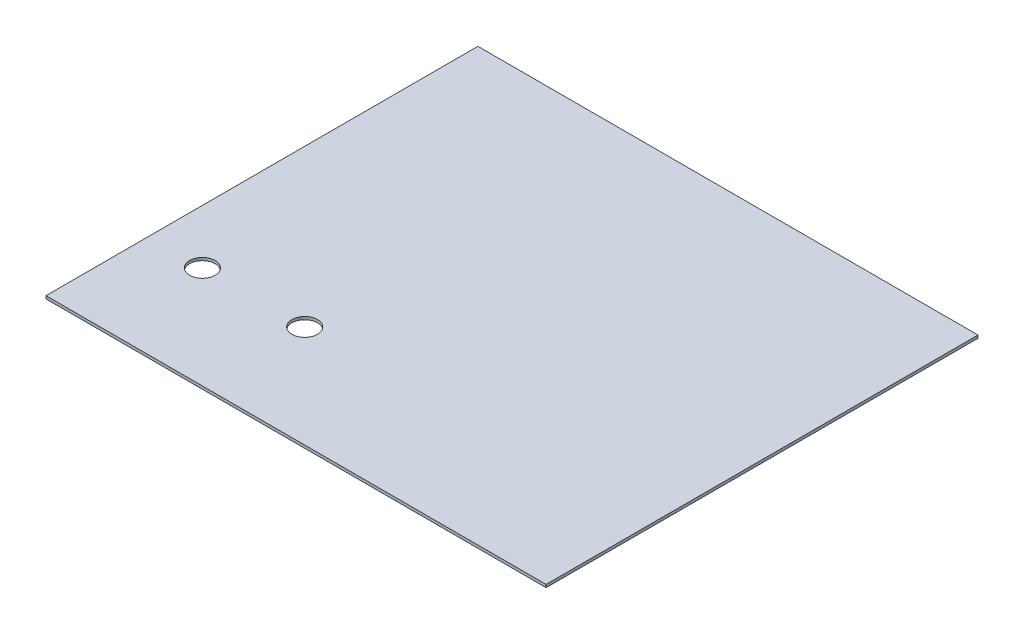
SolidWorks part; units mm, degrees
ref_plane "Front Plane" through (0, 0, 0) normal (0, 0, 1) x (1, 0, 0)
ref_plane "Top Plane" through (0, 0, 0) normal (0, 1, 0) x (1, 0, 0)
ref_plane "Right Plane" through (0, 0, 0) normal (1, 0, 0) x (0, 0, -1)
sketch "Sketch1" plane through (0, 0, 0) normal (0, 1, 0) x (1, 0, 0)
  line L1 (0, 0) -> (558.8, 0)
  line L2 (0, 0) -> (0, 482.6)
  line L3 (0, 482.6) -> (558.8, 482.6)
  line L4 (558.8, 0) -> (558.8, 482.6)
  dimension "D1" = 558.8
  dimension "D2" = 482.6
extrude "Boss-Extrude1" add sketch "Sketch1" along normal blind 3.175
sketch "Sketch2" plane through (0, 3.175, 0) normal (0, 1, 0) x (1, 0, 0)
  line L3 (60.4606, 114.3) -> (174.7606, 114.3) construction
  line L4 (0, 0) -> (558.8, 0) construction
  circle A2 centre (60.4606, 114.3) radius 14.2875
  circle A3 centre (174.7606, 114.3) radius 14.2875
  dimension "D3" = 28.575
  dimension "D4" = 28.575
  dimension "D5" = 114.3
  dimension "D8" = 114.3
extrude "Cut-Extrude1" cut sketch "Sketch2" against normal blind 3.175
